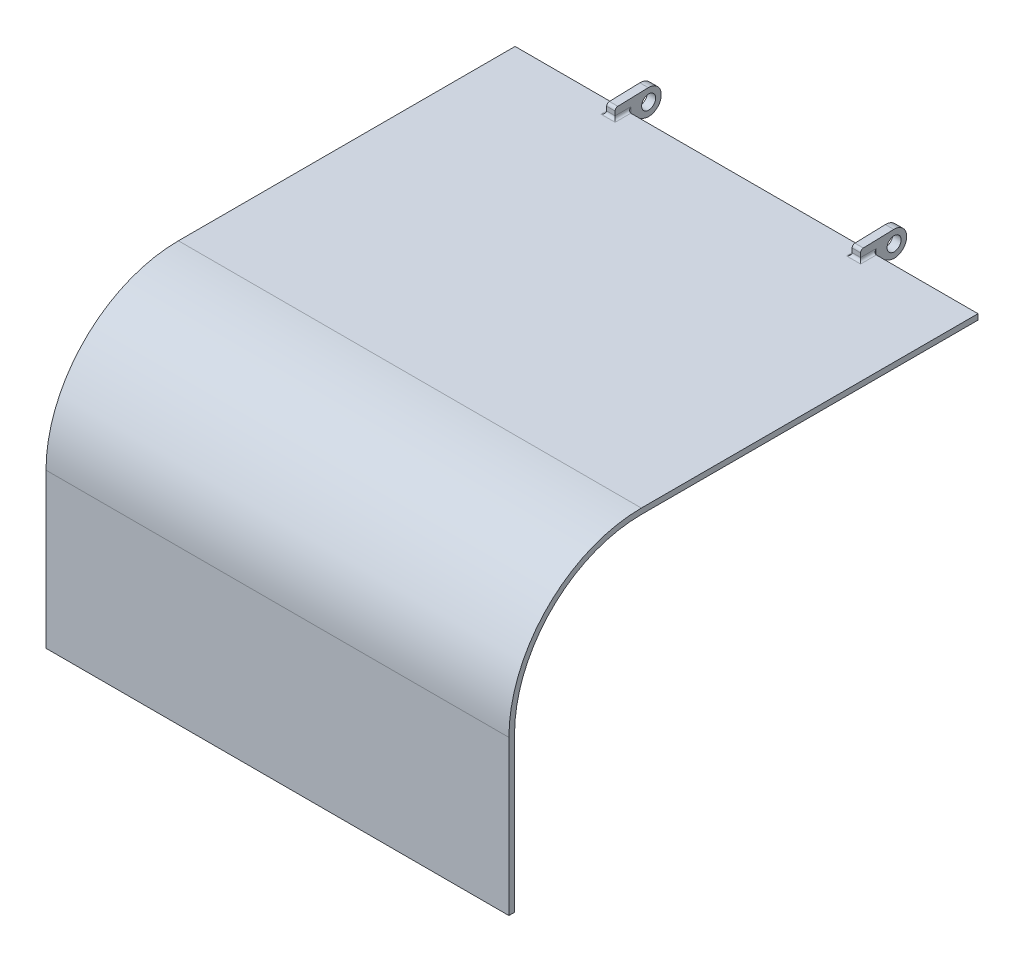
SolidWorks part; units mm, degrees
ref_plane "Front Plane" through (0, 0, 0) normal (0, 0, 1) x (1, 0, 0)
ref_plane "Top Plane" through (0, 0, 0) normal (0, 1, 0) x (1, 0, 0)
ref_plane "Right Plane" through (0, 0, 0) normal (1, 0, 0) x (0, 0, -1)
sketch "Sketch1" plane through (679.4749, 899.4363, 1292.8449) normal (1, 0, 0) x (0, 0, -1)
  line L3 (-167.2, 0) -> (-167.2, 55)
  line L4 (-120, 102.2) -> (0, 102.2)
  line L5 (-120, 100.2) -> (0, 100.2)
  line L6 (-165.2, 0) -> (-165.2, 55)
  line L7 (-120, 100.2) -> (0, 100.2)
  line L8 (-165.2, 0) -> (-165.2, 55)
  line L9 (-167.2, 0) -> (-165.2, 0)
  line L10 (0, 102.2) -> (0, 100.2)
  arc A2 (-120, 102.2) -> (-167.2, 55) centre (-120, 55) ccw
  arc A3 (-120, 100.2) -> (-165.2, 55) centre (-120, 55) ccw
  arc A4 (-120, 100.2) -> (-165.2, 55) centre (-120, 55) ccw
  dimension "D1" = 0.2
  dimension "D2" = 2
extrude "Boss-Extrude1" add sketch "Sketch1" along normal mid plane 165
ref_plane "Plane1" through (721.7249, 0, 0) normal (1, 0, 0) x (0, 0, -1)
sketch "Sketch2" plane through (721.7249, 0, 0) normal (1, 0, 0) x (0, 0, -1)
  line L0 (-1292.8449, 999.6363) -> (-1287.5497, 996.9142)
  line L1 (-1297.4484, 1001.6363) -> (-1297.4484, 1005.0707)
  line L2 (-1297.4484, 1005.0707) -> (-1285.6231, 1005.4145)
  line L3 (-1297.4484, 1001.6363) -> (-1292.8449, 1001.6363)
  line L4 (-1292.8449, 1001.6363) -> (-1292.8449, 999.6363)
  arc A0 (-1287.5497, 996.9142) -> (-1285.6231, 1005.4145) centre (-1285.4924, 1000.9164) ccw
  circle A1 centre (-1285.4924, 1000.9164) radius 2.5 construction
  arc A2 (-1282.135, 997.92) -> (-1288.8497, 1003.9128) centre (-1285.4924, 1000.9164) ccw construction
  circle A3 centre (-1285.4924, 1000.9164) radius 2.5
  dimension "D1" = 5
extrude "Boss-Extrude2" add sketch "Sketch2" along normal blind 3
fillet "Fillet1" radius 1 6 edges at (721.7249, 1000.6363, 1292.8449) (724.7249, 1000.6363, 1292.8449) (723.2249, 1005.0707, 1297.4484) (721.7249, 1001.6363, 1295.1467) (723.2249, 1001.6363, 1297.4484) (724.7249, 1001.6363, 1295.1467)
ref_plane "plano medio" through (679.4749, 0, 0) normal (1, 0, 0) x (0, 0, -1)
mirror "Mirror1" about plane through (679.4749, 0, 0) normal (1, 0, 0) of "Fillet1", "Boss-Extrude2"
sketch "Sketch3" plane through (679.4749, 0, 0) normal (1, 0, 0) x (0, 0, -1)
  line L0 (-1458.0449, 907.7606) -> (-1456.4449, 907.7606)
  line L1 (-1455.9449, 907.2606) -> (-1455.9449, 904.2606)
  line L2 (-1455.9449, 904.2606) -> (-1453.9449, 904.2606)
  line L3 (-1453.9449, 904.2606) -> (-1453.9449, 909.7606)
  line L4 (-1453.9449, 909.7606) -> (-1458.0449, 909.7606)
  line L5 (-1458.0449, 909.7606) -> (-1458.0449, 907.7606)
  line L6 (-1458.0449, 899.4363) -> (-1458.0449, 954.4363) construction
  line L7 (-1456.4449, 907.7606) -> (-1455.9449, 907.7606) construction
  line L8 (-1455.9449, 907.7606) -> (-1455.9449, 907.2606) construction
  arc A0 (-1456.4449, 907.7606) -> (-1455.9449, 907.2606) centre (-1455.9449, 907.7606) cw
  dimension "D5" = 0.5
  dimension "D1" = 2
  dimension "D2" = 2
  dimension "D3" = 2.1
  dimension "D4" = 3.5
extrude "Boss-Extrude3" add sketch "Sketch3" along normal mid plane 50 contours L4 L5 L0 A0 L1 L2 L3
fillet "Fillet2" radius 2 1 edges at (679.4749, 904.2606, 1455.9449)
fillet "Fillet3" radius 0.5 8 edges at (654.4749, 909.7606, 1455.9949) (654.4749, 908.7606, 1458.0449) (704.4749, 908.7606, 1458.0449) (704.4749, 909.7606, 1455.9949) (679.4749, 909.7606, 1458.0449) (679.4749, 909.7606, 1453.9449)
